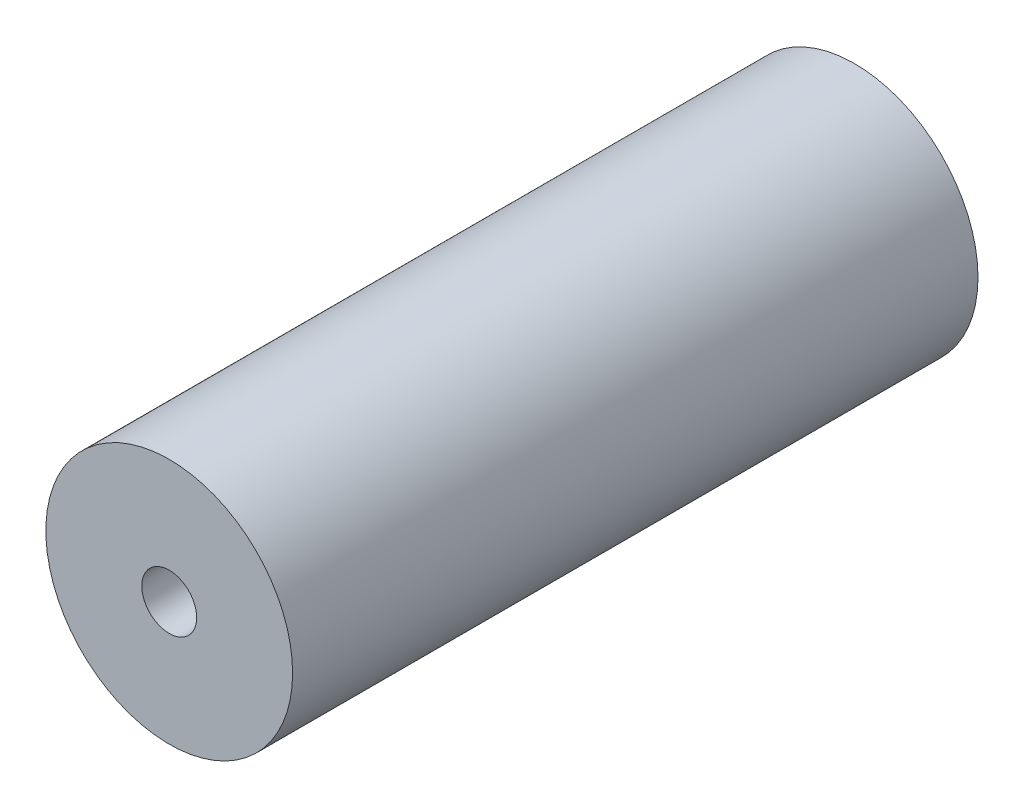
SolidWorks part; units mm, degrees
material "Cast Alloy Steel"
ref_plane "Front Plane" through (0, 0, 0) normal (0, 0, 1) x (1, 0, 0)
ref_plane "Top Plane" through (0, 0, 0) normal (0, 1, 0) x (1, 0, 0)
ref_plane "Right Plane" through (0, 0, 0) normal (1, 0, 0) x (0, 0, -1)
sketch "Sketch2" plane through (0, 0, 0) normal (0, 0, 1) x (1, 0, 0)
  circle A0 centre (0, 0) radius 18
extrude "Boss-Extrude1" add sketch "Sketch2" along normal blind 50 and the other way blind 50
sketch "Sketch3" plane through (0, 0, 50) normal (0, 0, 1) x (1, 0, 0)
  circle A0 centre (0, 0) radius 4
  dimension "D1" = 0
extrude "Cut-Extrude1" cut sketch "Sketch3" against normal blind 122
sketch "Sketch4" plane through (0, 0, -50) normal (0, 0, -1) x (-1, 0, 0)
  line L0 (0, 35.8542) -> (0, -31.7202) construction
  line L1 (-38.0006, 0) -> (55.6495, 0) construction
  circle A0 centre (0, 0) radius 14 construction
  circle A1 centre (0, 14) radius 1.5
  circle A2 centre (14, 0) radius 1.5
  circle A3 centre (0, -14) radius 1.5
  circle A4 centre (-14, 0) radius 1.5
extrude "Cut-Extrude2" cut sketch "Sketch4" against normal blind 5
